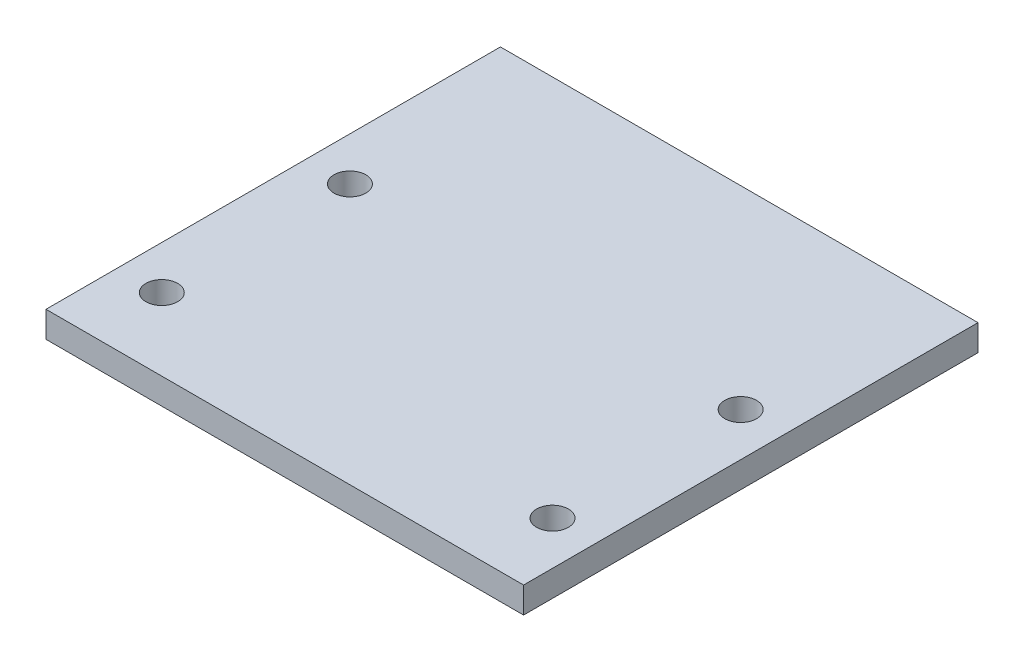
SolidWorks part; units mm, degrees
ref_plane "Front Plane" through (0, 0, 0) normal (0, 0, 1) x (1, 0, 0)
ref_plane "Top Plane" through (0, 0, 0) normal (0, 1, 0) x (1, 0, 0)
ref_plane "Right Plane" through (0, 0, 0) normal (1, 0, 0) x (0, 0, -1)
sketch "Sketch5" plane through (0, 0, 0) normal (0, 1, 0) x (1, 0, 0)
  line L0 (0, 0) -> (-41.91, 0)
  line L1 (-41.91, 0) -> (-41.91, -39.878)
  line L2 (-41.91, -39.878) -> (0, -39.878)
  line L3 (0, -39.878) -> (0, 0)
  line L4 (-41.91, -39.878) -> (-38.1, -39.878) construction
  line L5 (-38.1, -39.878) -> (-38.1, -33.528) construction
  line L6 (-20.955, -39.878) -> (-20.955, 0) construction
  line L7 (-38.1, -39.878) -> (-38.1, -17.018) construction
  circle A0 centre (-38.1, -17.018) radius 1.397
  circle A1 centre (-38.1, -33.528) radius 1.397
  circle A2 centre (-3.81, -33.528) radius 1.397
  circle A3 centre (-3.81, -17.018) radius 1.397
extrude "Extrude3" add sketch "Sketch5" along normal blind 2.286 separate body
